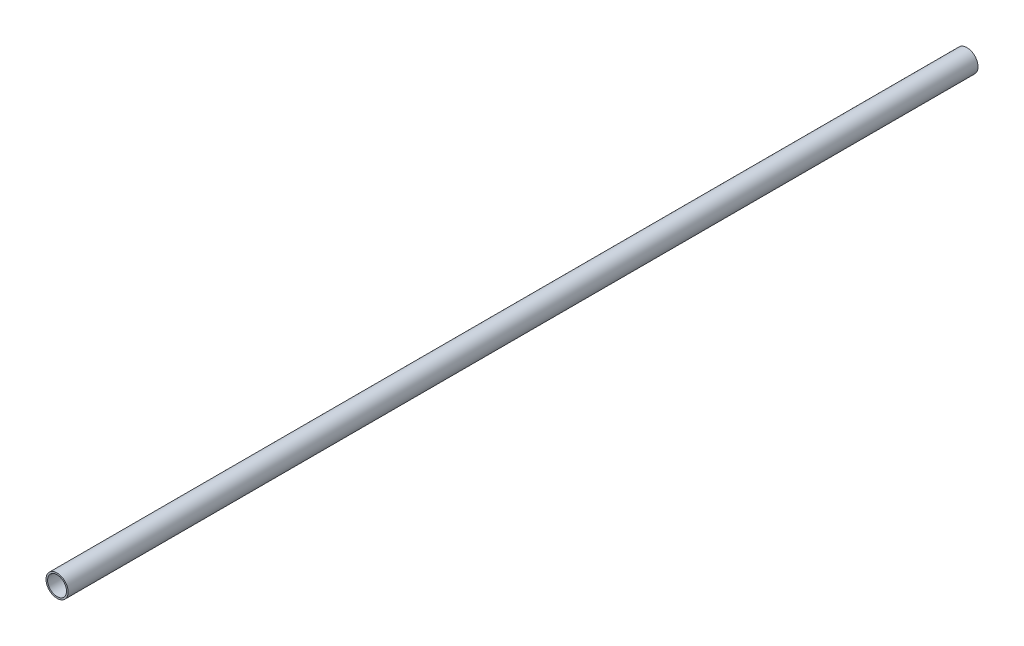
SolidWorks part; units mm, degrees
ref_plane "Front Plane" through (0, 0, 0) normal (0, 0, 1) x (1, 0, 0)
ref_plane "Top Plane" through (0, 0, 0) normal (0, 1, 0) x (1, 0, 0)
ref_plane "Right Plane" through (0, 0, 0) normal (1, 0, 0) x (0, 0, -1)
sketch "Sketch1" plane through (0, 0, 0) normal (0, 0, 1) x (1, 0, 0)
  line L4 (-22.225, 0) -> (-19.05, 0) construction
  circle A0 centre (0, 0) radius 22.225
  circle A1 centre (0, 0) radius 19.05
  dimension "OD" = 44.45
  dimension "ID" = 38.1
sketch "Sketch2" plane through (0, 0, 0) normal (1, 0, 0) x (0, 0, -1)
  line L0 (-914.4, 22.225) -> (914.4, 22.225) construction
  point P2 (0, 22.225)
  point P3 (-869.95, 22.225)
  point P5 (869.95, 22.225)
  dimension "Length" = 1828.8
  dimension "D1" = 44.45
  dimension "D2" = 44.45
extrude "Boss-Extrude1" add sketch "Sketch1" along normal up to vertex (914.4 mm away) and the other way up to vertex (914.4 mm away) up to point (0, 22.225, 914.4) other way up to point (0, 22.225, -914.4)
equation "\"D1@Sketch2\"=\"OD@Sketch1\""
equation "\"D2@Sketch2\"=\"D1@Sketch2\""
